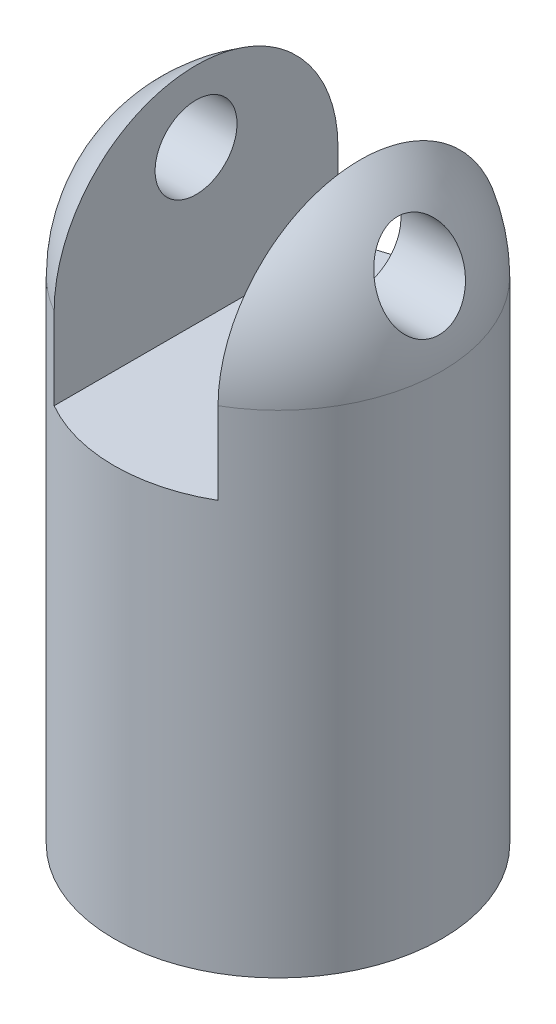
SolidWorks part; units mm, degrees
material "6061-T6 (SS)"
ref_plane "Front Plane" through (0, 0, 0) normal (0, 0, 1) x (1, 0, 0)
ref_plane "Top Plane" through (0, 0, 0) normal (0, 1, 0) x (1, 0, 0)
ref_plane "Right Plane" through (0, 0, 0) normal (1, 0, 0) x (0, 0, -1)
sketch "Sketch1" plane through (0, 0, 0) normal (0, 0, 1) x (1, 0, 0)
  line L0 (0, -50.8) -> (0, 50.8)
  line L1 (25.4, 25.4) -> (25.4, -50.8)
  line L2 (25.4, -50.8) -> (0, -50.8)
  arc A0 (0, 50.8) -> (25.4, 25.4) centre (0, 25.4) cw
  dimension "D1" = 25.4
  dimension "D2" = 101.6
revolve "Revolve3" add sketch "Sketch1" angle 360 about L0
sketch "Sketch2" plane through (0, 0, 0) normal (0, 0, 1) x (1, 0, 0)
  line L1 (-12.7, 50.8) -> (12.7, 50.8)
  line L2 (-12.7, 50.8) -> (-12.7, 12.7)
  line L3 (-12.7, 12.7) -> (12.7, 12.7)
  line L4 (12.7, 50.8) -> (12.7, 12.7)
  line L5 (-12.7, 50.8) -> (12.7, 12.7) construction
  line L6 (-12.7, 12.7) -> (12.7, 50.8) construction
  arc A0 (25.4, 25.4) -> (-25.4, 25.4) centre (0, 25.4) ccw construction
  point P0 (0, 31.75)
  dimension "D1" = 25.4
  dimension "D2" = 38.1
extrude "Cut-Extrude1" cut sketch "Sketch2" against normal mid plane 203.2
sketch "Sketch3" plane through (-12.7, 0, 0) normal (1, 0, 0) x (0, 0, -1)
  line L0 (0, 25.4) -> (0, 47.397) construction
  line L2 (21.997, 25.4) -> (-21.997, 25.4) construction
  arc A0 (21.997, 25.4) -> (-21.997, 25.4) centre (0, 25.4) ccw construction
  circle A1 centre (0, 36.3985) radius 6.35
  dimension "D1" = 12.7
extrude "Cut-Extrude2" cut sketch "Sketch3" against normal mid plane 203.2
sketch "Sketch4" plane through (0, -50.8, 0) normal (0, -1, 0) x (1, 0, 0)
  circle A0 centre (0, 0) radius 6.35
  dimension "D1" = 12.7
extrude "Cut-Extrude3" cut sketch "Sketch4" against normal blind 25.4
ref_axis "Axis1" through (-20.3456, 36.3985, 0) along (1, 0, 0)
sketch "Sketch5" plane through (0, 0, 0) normal (1, 0, 0) x (0, 0, -1)
  point P0 (0, 36.3985)
